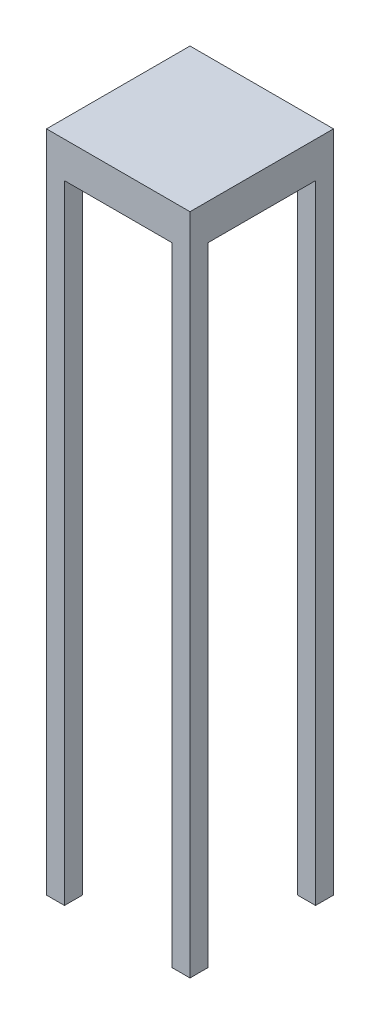
SolidWorks part; units mm, degrees
ref_plane "Alzado" through (0, 0, 0) normal (0, 0, 1) x (1, 0, 0)
ref_plane "Planta" through (0, 0, 0) normal (0, 1, 0) x (1, 0, 0)
ref_plane "Vista lateral" through (0, 0, 0) normal (1, 0, 0) x (0, 0, -1)
sketch "Croquis1" plane through (0, 0, 0) normal (0, 1, 0) x (1, 0, 0)
  line L1 (0, 0) -> (200, 0)
  line L2 (0, 0) -> (0, 200)
  line L3 (0, 200) -> (200, 200)
  line L4 (200, 0) -> (200, 200)
  dimension "D1" = 200
  dimension "D2" = 200
extrude "Saliente-Extruir1" add sketch "Croquis1" along normal blind 50
sketch "Croquis2" plane through (0, 0, 0) normal (0, -1, 0) x (1, 0, 0)
  line L1 (0, 0) -> (25, 0)
  line L2 (0, 0) -> (0, -25)
  line L3 (0, -25) -> (25, -25)
  line L4 (25, 0) -> (25, -25)
  line L5 (200, 0) -> (175, 0)
  line L6 (200, 0) -> (200, -25)
  line L7 (200, -25) -> (175, -25)
  line L8 (175, 0) -> (175, -25)
  line L9 (0, -200) -> (25, -200)
  line L10 (0, -200) -> (0, -175)
  line L11 (0, -175) -> (25, -175)
  line L12 (25, -200) -> (25, -175)
  line L13 (200, -200) -> (175, -200)
  line L14 (200, -200) -> (200, -175)
  line L15 (200, -175) -> (175, -175)
  line L16 (175, -200) -> (175, -175)
  point P23 (0, 0)
extrude "Saliente-Extruir2" add sketch "Croquis2" along normal blind 875
